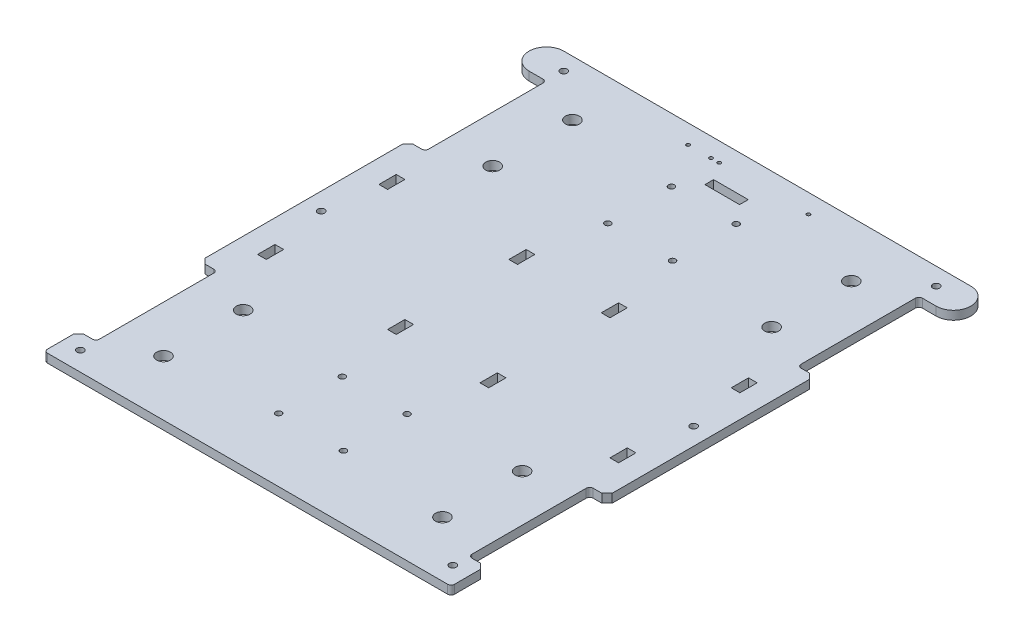
SolidWorks part; units mm, degrees
material "Teak"
ref_plane "Front Plane" through (0, 0, 0) normal (0, 0, 1) x (1, 0, 0)
ref_plane "Top Plane" through (0, 0, 0) normal (0, 1, 0) x (1, 0, 0)
ref_plane "Right Plane" through (0, 0, 0) normal (1, 0, 0) x (0, 0, -1)
sketch "Sketch1" plane through (0, 0, 0) normal (0, 1, 0) x (1, 0, 0)
  line L0 (0, 170) -> (0, -130) construction
  line L1 (-117.5, 0) -> (117.5, 0) construction
  line L2 (-117.5, -130) -> (117.5, -130)
  line L3 (117.5, -130) -> (117.5, -110)
  line L4 (117.5, -110) -> (107.5, -110)
  line L5 (107.5, -110) -> (107.5, -40)
  line L6 (107.5, -40) -> (117.5, -40)
  line L7 (117.5, -40) -> (117.5, 80)
  line L8 (117.5, 80) -> (107.5, 80)
  line L9 (107.5, 80) -> (107.5, 150)
  line L10 (107.5, 150) -> (127.5, 150)
  line L11 (-107.5, 150) -> (-127.5, 150)
  line L12 (-107.5, 80) -> (-107.5, 150)
  line L13 (-117.5, 80) -> (-107.5, 80)
  line L14 (-117.5, -40) -> (-117.5, 80)
  line L15 (-107.5, -40) -> (-117.5, -40)
  line L16 (-107.5, -110) -> (-107.5, -40)
  line L17 (-117.5, -110) -> (-107.5, -110)
  line L18 (-117.5, -130) -> (-117.5, -110)
  line L19 (127.5, 150) -> (127.5, 170)
  line L20 (127.5, 170) -> (-127.5, 170)
  line L21 (-127.5, 150) -> (-127.5, 170)
  point P5 (0, 0)
  dimension "D1" = 300
  dimension "D2" = 20
  dimension "D3" = 20
  dimension "D5" = 10
  dimension "D6" = 70
  dimension "D7" = 70
  dimension "D8" = 255
  dimension "D9" = 20
extrude "Boss-Extrude1" add sketch "Sketch1" along normal blind 5
fillet "Fillet3" 2 edges at (127.5, 2.5, -150) (127.5, 2.5, -170) type full round first side face at (117.5, 2.5, -150) second side face at (0, 2.5, -170) middle face at (127.5, 2.5, -160)
fillet "Fillet4" 2 edges at (-127.5, 2.5, -170) (-127.5, 2.5, -150) type full round first side face at (-5, 2.5, -170) second side face at (-117.5, 2.5, -150) middle face at (-127.5, 2.5, -160)
fillet "Fillet2" radius 2 10 edges at (107.5, 2.5, 40) (107.5, 2.5, -150) (107.5, 2.5, -80) (107.5, 2.5, 110) (-107.5, 2.5, -80) (-107.5, 2.5, 110) (-107.5, 2.5, 40) (-107.5, 2.5, -150) (-117.5, 2.5, 130) (117.5, 2.5, 130)
sketch "Sketch2" plane through (0, 5, 0) normal (0, 1, 0) x (1, 0, 0)
  line L0 (0, -130) -> (0, 90) construction
  line L1 (-115.5, -130) -> (115.5, -130) construction
  line L2 (107.5, 82) -> (107.5, 148) construction
  line L4 (117.5, -40) -> (117.5, 80) construction
  line L5 (117.5, -128) -> (117.5, -110) construction
  arc A0 (117.5, 150) -> (117.5, 170) centre (117.5, 160) ccw construction
  circle A1 centre (107.5, 160) radius 2
  circle A2 centre (107.5, 20) radius 2
  circle A3 centre (107.5, -119) radius 2
  circle A5 centre (-107.5, -119) radius 2
  circle A6 centre (-107.5, 20) radius 2
  circle A7 centre (-107.5, 160) radius 2
  point P17 (127.5, 160)
  point P26 (117.5, 20)
  point P30 (117.5, -119)
  dimension "D1" = 4
  dimension "D3" = 10
extrude "layer fix hole" cut sketch "Sketch2" against normal through all
chamfer "Chamfer1" distance 3 angle 45 6 edges at (117.5, 2.5, 110) (-117.5, 2.5, -80) (-117.5, 2.5, 40) (-117.5, 2.5, 110) (117.5, 2.5, -80) (117.5, 2.5, 40)
sketch "Sketch9" plane through (0, 0, 0) normal (0, -1, 0) x (1, 0, 0)
  line L0 (107.5, -115) -> (-119.4618, -115) construction
  line L1 (107.5, -82) -> (107.5, -148) construction
  line L2 (107.5, 75) -> (-117.246, 75) construction
  line L3 (107.5, 108) -> (107.5, 42) construction
  line L4 (-117.5, -20) -> (128.0189, -20) construction
  line L5 (0, 75) -> (0, -115) construction
  line L6 (-80.5, -96.3983) -> (-80.5, -133.6017) construction
  line L7 (-107.5, -148) -> (-107.5, -82) construction
  line L8 (-117.5, -77) -> (-117.5, 37) construction
  circle A0 centre (-80.5, -138) radius 4
  circle A1 centre (-80.5, -92) radius 4
  circle A2 centre (80.5, -92) radius 4
  circle A3 centre (80.5, -138) radius 4
  circle A4 centre (80.5, 98) radius 4
  circle A5 centre (80.5, 52) radius 4
  circle A6 centre (-80.5, 98) radius 4
  circle A7 centre (-80.5, 52) radius 4
  point P16 (-80.5, -115)
  dimension "D2" = 8
  dimension "D1" = 27
  dimension "D3" = 23
extrude "Motor fix hole" cut sketch "Sketch9" against normal up to next
sketch "Sketch10" plane through (0, 0, 0) normal (0, -1, 0) x (1, 0, 0)
  line L0 (-117.5, -20) -> (130.9103, -20) construction
  line L1 (-117.5, -77) -> (-117.5, 37) construction
  line L2 (0, 130) -> (0, -170) construction
  line L3 (-115.5, 130) -> (115.5, 130) construction
  line L4 (117.5, -170) -> (-117.5, -170) construction
  line L5 (-18.6898, 56.6291) -> (18.6898, 56.6291) construction
  line L6 (-23.6898, 98.3709) -> (23.6898, 98.3709) construction
  line L7 (-23.6898, 98.3709) -> (-23.6898, 51.6291) construction
  line L8 (-23.6898, 51.6291) -> (23.6898, 51.6291) construction
  line L9 (23.6898, 98.3709) -> (23.6898, 51.6291) construction
  line L10 (-23.6898, 98.3709) -> (23.6898, 51.6291) construction
  line L11 (-23.6898, 51.6291) -> (23.6898, 98.3709) construction
  line L12 (18.6898, 93.3709) -> (18.6898, 56.6291) construction
  line L13 (-18.6898, 93.3709) -> (18.6898, 93.3709) construction
  line L14 (-18.6898, 93.3709) -> (-18.6898, 56.6291) construction
  line L18 (-18.6898, -133.3709) -> (-18.6898, -96.6291) construction
  line L19 (-18.6898, -133.3709) -> (18.6898, -133.3709) construction
  line L25 (18.6898, -133.3709) -> (18.6898, -96.6291) construction
  line L28 (-23.6898, -91.6291) -> (23.6898, -138.3709) construction
  line L29 (-107.5, 75) -> (107.5, 75) construction
  line L30 (-23.6898, -138.3709) -> (23.6898, -91.6291) construction
  line L32 (23.6898, -138.3709) -> (23.6898, -91.6291) construction
  line L33 (-23.6898, -91.6291) -> (23.6898, -91.6291) construction
  line L34 (-23.6898, -138.3709) -> (-23.6898, -91.6291) construction
  line L35 (-107.5, 42) -> (-107.5, 108) construction
  line L36 (-23.6898, -138.3709) -> (23.6898, -138.3709) construction
  line L37 (-18.6898, -96.6291) -> (18.6898, -96.6291) construction
  line L38 (107.5, 108) -> (107.5, 42) construction
  circle A0 centre (18.6898, 56.6291) radius 1.75
  circle A1 centre (-18.6898, 56.6291) radius 1.75
  circle A2 centre (-18.6898, 93.3709) radius 1.75
  circle A3 centre (18.6898, 93.3709) radius 1.75
  circle A4 centre (18.6898, -133.3709) radius 1.75
  circle A5 centre (-18.6898, -133.3709) radius 1.75
  circle A6 centre (-18.6898, -96.6291) radius 1.75
  circle A7 centre (18.6898, -96.6291) radius 1.75
  point P10 (0, 75)
  point P37 (0, -115)
  dimension "D3" = 3.5
  dimension "D1" = 37.3795
  dimension "D2" = 5
  dimension "D4" = 36.7418
extrude "Motor driver fix hole" cut sketch "Sketch10" against normal up to next
sketch "Sketch11" plane through (0, 0, 0) normal (0, -1, 0) x (1, 0, 0)
  line L0 (0, -170) -> (0, -144.1108) construction
  line L1 (117.5, -170) -> (-117.5, -170) construction
  line L2 (0, -144.1108) -> (0, -110.0028) construction
  line L5 (-37.465, -159) -> (37.465, -159) construction
  line L7 (34.2319, -158.1371) -> (37.465, -159) construction
  line L8 (-37.465, -159) -> (-34.2319, -158.1371) construction
  line L10 (-10, -144) -> (10, -144)
  line L11 (-10, -144) -> (-10, -149)
  line L12 (-10, -149) -> (10, -149)
  line L13 (10, -144) -> (10, -149)
  line L14 (-10, -144) -> (10, -149) construction
  line L15 (-10, -149) -> (10, -144) construction
  circle A0 centre (-34.7373, -159) radius 1
  circle A1 centre (-21.5138, -159) radius 1
  circle A2 centre (-16.8148, -159) radius 1
  circle A3 centre (34.7373, -159) radius 1
  point P1 (0, -146.5)
  point P5 (0, -149.001)
  dimension "D2" = 2.7277
  dimension "D6" = 2
  dimension "D1" = 2.7277
  dimension "D3" = 13.2235
  dimension "D4" = 4.699
  dimension "D5" = 51.5521
  dimension "D7" = 20
  dimension "D8" = 5
  dimension "D9" = 11
  dimension "D10" = 10
extrude "QTR8a fix hole" cut sketch "Sketch11" against normal blind 10
sketch "Sketch 12" plane through (0, 5, 0) normal (0, 1, 0) x (1, 0, 0)
  line L0 (-39.1667, 170) -> (-39.1667, -135.4982) construction
  line L1 (117.5, 170) -> (-117.5, 170) construction
  line L2 (-117.5, 20) -> (117.5, 20) construction
  line L12 (24.1667, 60) -> (29.1667, 60)
  line L37 (-117.5, -120.5) -> (-39.1667, -120.5) construction
  line L38 (39.1667, 170) -> (39.1667, -135.4982) construction
  line L39 (-39.1667, -120.5) -> (39.1667, -120.5) construction
  line L40 (39.1667, -120.5) -> (117.5, -120.5) construction
  line L41 (117.5, -128) -> (117.5, -113) construction
  line L42 (-117.5, -113) -> (-117.5, -128) construction
  line L43 (99.1667, 60) -> (99.1667, 50)
  line L44 (24.1667, 60) -> (24.1667, 50)
  line L45 (24.1667, 50) -> (29.1667, 50)
  line L46 (29.1667, 60) -> (29.1667, 50)
  line L86 (-117.5, 77) -> (-117.5, -37) construction
  line L87 (117.5, -37) -> (117.5, 77) construction
  line L88 (24.1667, -10) -> (29.1667, -10)
  line L89 (29.1667, -20) -> (29.1667, -10)
  line L90 (24.1667, -20) -> (29.1667, -20)
  line L91 (24.1667, -20) -> (24.1667, -10)
  line L92 (99.1667, 60) -> (104.1667, 60)
  line L93 (104.1667, 60) -> (104.1667, 50)
  line L94 (99.1667, 50) -> (104.1667, 50)
  line L95 (99.1667, -10) -> (104.1667, -10)
  line L96 (104.1667, -20) -> (104.1667, -10)
  line L97 (99.1667, -20) -> (104.1667, -20)
  line L98 (99.1667, -20) -> (99.1667, -10)
  line L99 (-104.1667, 60) -> (-99.1667, 60)
  line L100 (-29.1667, 60) -> (-29.1667, 50)
  line L101 (-104.1667, 60) -> (-104.1667, 50)
  line L102 (-104.1667, 50) -> (-99.1667, 50)
  line L103 (-99.1667, 60) -> (-99.1667, 50)
  line L104 (-104.1667, -10) -> (-99.1667, -10)
  line L105 (-99.1667, -20) -> (-99.1667, -10)
  line L106 (-104.1667, -20) -> (-99.1667, -20)
  line L107 (-104.1667, -20) -> (-104.1667, -10)
  line L108 (-29.1667, 60) -> (-24.1667, 60)
  line L109 (-24.1667, 60) -> (-24.1667, 50)
  line L110 (-29.1667, 50) -> (-24.1667, 50)
  line L111 (-29.1667, -10) -> (-24.1667, -10)
  line L112 (-24.1667, -20) -> (-24.1667, -10)
  line L113 (-29.1667, -20) -> (-24.1667, -20)
  line L114 (-29.1667, -20) -> (-29.1667, -10)
  line L115 (-245.8333, 20) -> (-10.8333, 20) construction
  line L117 (-89.1667, 170) -> (-89.1667, -135.4982) construction
  point P0 (29.1667, 55)
  dimension "D1" = 5
  dimension "D2" = 10
  dimension "D3" = 10
  dimension "D4" = 2
  dimension "D7" = 60
  dimension "D8" = 10
  dimension "D5" = 2
  dimension "D6" = 70
extrude "Battery fixed hole" cut sketch "Sketch 12" against normal through all
sketch "Sketch12" plane through (0, 5, 0) normal (0, 1, 0) x (1, 0, 0)
